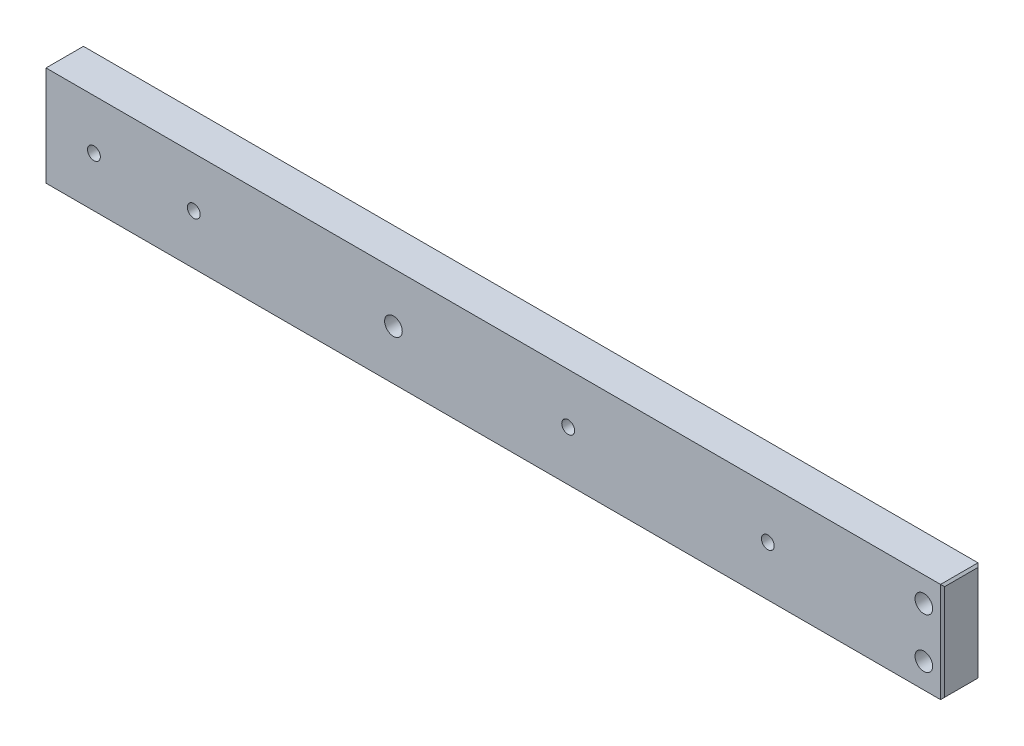
SolidWorks part; units mm, degrees
material "6061-T6 (SS)"
ref_plane "Front Plane" through (0, 0, 0) normal (0, 0, 1) x (1, 0, 0)
ref_plane "Top Plane" through (0, 0, 0) normal (0, 1, 0) x (1, 0, 0)
ref_plane "Right Plane" through (0, 0, 0) normal (1, 0, 0) x (0, 0, -1)
sketch "Sketch1" plane through (0, 0, 0) normal (0, 0, 1) x (1, 0, 0)
  line L1 (0, 0) -> (-228.6, 0)
  line L2 (0, 0) -> (0, 25.4)
  line L3 (0, 25.4) -> (-228.6, 25.4)
  line L4 (-228.6, 0) -> (-228.6, 25.4)
  dimension "D1" = 25.4
  dimension "D2" = 228.6
extrude "Boss-Extrude1" add sketch "Sketch1" along normal blind 9.525
sketch "Sketch2" plane through (0, 0, 9.525) normal (0, 0, 1) x (1, 0, 0)
  line L0 (-4.7625, 6.35) -> (-4.7625, 19.05)
  line L1 (-4.7625, 19.05) -> (-4.7625, 25.4)
  line L2 (0, 25.4) -> (-228.6, 25.4) construction
  line L3 (-4.7625, 6.35) -> (-4.7625, 0)
  line L4 (-228.6, 0) -> (0, 0) construction
  line L5 (0, 0) -> (0, 25.4) construction
  dimension "D1" = 4.7625
  dimension "D2" = 12.7
hole_wizard "#8 Clearance Hole1" positions "Sketch3" profile "Sketch4" hole size "#8" standard "ANSI Inch"
sketch "Sketch3" plane through (0, 0, 9.525) normal (0, 0, 1) x (1, 0, 0)
  point P0 (-4.7625, 6.35)
  point P3 (-4.7625, 19.05)
sketch "Sketch4" plane through (-4.7625, 6.35, 9.525) normal (1, 0, 0) x (0, -1, 0)
  line L0 (0, 0) -> (0, 26.7507)
  line L1 (0, 26.7507) -> (2.2479, 25.4)
  line L2 (2.2479, 25.4) -> (2.2479, 0)
  line L5 (2.2479, 0) -> (0, 0)
  line L10 (0, 26.7507) -> (-2.2479, 25.4) construction
  line L11 (0, -6.35) -> (0, 107.95) construction
  dimension "Hole Dia." = 4.4958
  dimension "Hole Depth" = 25.4
  dimension "Drill Angle" = 118
hole_wizard "#8 Clearance Hole2" positions "Sketch8" profile "Sketch9" hole size "#8" standard "ANSI Inch"
sketch "Sketch8" plane through (0, 0, 9.525) normal (0, 0, 1) x (1, 0, 0)
  line L0 (-203.2, 12.7) -> (-139.7, 12.7)
  line L1 (-203.2, 12.7) -> (-228.6, 12.7)
  line L2 (-228.6, 25.4) -> (-228.6, 0) construction
  point P2 (-139.7, 12.7)
  dimension "D1" = 63.5
  dimension "D2" = 25.4
sketch "Sketch9" plane through (-139.7, 12.7, 9.525) normal (1, 0, 0) x (0, -1, 0)
  line L0 (0, 0) -> (0, 20.4007)
  line L1 (0, 20.4007) -> (2.2479, 19.05)
  line L2 (2.2479, 19.05) -> (2.2479, 0)
  line L5 (2.2479, 0) -> (0, 0)
  line L10 (0, 20.4007) -> (-2.2479, 19.05) construction
  line L11 (0, -6.35) -> (0, 107.95) construction
  dimension "Hole Dia." = 4.4958
  dimension "Hole Depth" = 19.05
  dimension "Drill Angle" = 118
chamfer "Chamfer1" distance 0.508 angle 45 8 edges at (0, 0, 4.7625) (0, 12.7, 9.525) (0, 25.4, 4.7625) (0, 12.7, 0) (-228.6, 25.4, 4.7625) (-228.6, 12.7, 9.525) (-228.6, 0, 4.7625) (-228.6, 12.7, 0)
hole_wizard "#4 Clearance Hole1" positions "Sketch10" profile "Sketch12" hole size "#4" standard "ANSI Inch" end condition through all
sketch "Sketch10" plane through (0, 0, 0) normal (0, 0, -1) x (-1, 0, 0)
  point P0 (95.25, 12.7)
  point P3 (44.45, 12.7)
sketch "Sketch12" plane through (-95.25, 12.7, 0) normal (1, 0, 0) x (0, 1, 0)
  line L0 (0, 0) -> (0, 9.525)
  line L1 (0, 9.525) -> (1.6319, 9.525)
  line L2 (1.6319, 9.525) -> (1.6319, 0)
  line L5 (1.6319, 0) -> (0, 0)
  line L11 (0, -6.35) -> (0, 107.95) construction
  dimension "Thru Hole Dia." = 3.2639
  dimension "Thru Hole Depth" = 9.525
hole_wizard "#4 Clearance Hole2" positions "Sketch13" profile "Sketch14" hole size "#4" standard "ANSI Inch" end condition up to next
sketch "Sketch13" plane through (0, 0, 9.525) normal (0, 0, 1) x (1, 0, 0)
  line L0 (-215.9, 12.7) -> (-190.5, 12.7)
  line L2 (-228.092, 25.4) -> (-228.092, 0) construction
  line L3 (-139.7, 12.7) -> (-203.2, 12.7) construction
  point P0 (-215.9, 12.7)
  point P2 (-190.5, 12.7)
  point P11 (-228.092, 12.7)
  dimension "D1" = 25.4
  dimension "D2" = 63.5
sketch "Sketch14" plane through (-215.9, 12.7, 9.525) normal (1, 0, 0) x (0, -1, 0)
  line L0 (0, 0) -> (0, 9.525)
  line L1 (0, 9.525) -> (1.6319, 9.525)
  line L2 (1.6319, 9.525) -> (1.6319, 0)
  line L5 (1.6319, 0) -> (0, 0)
  line L11 (0, -6.35) -> (0, 107.95) construction
  dimension "Thru Hole Dia." = 3.2639
  dimension "Thru Hole Depth" = 9.525
